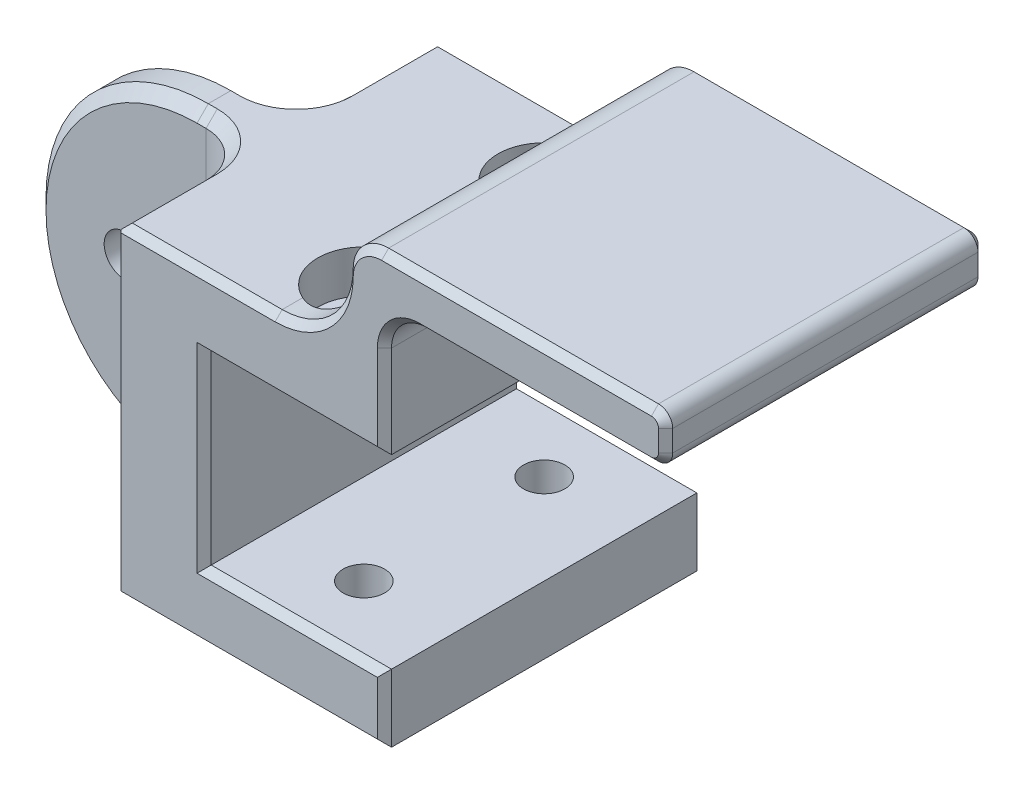
SolidWorks part; units mm, degrees
ref_plane "Front Plane" through (0, 0, 0) normal (0, 0, 1) x (1, 0, 0)
ref_plane "Top Plane" through (0, 0, 0) normal (0, 1, 0) x (1, 0, 0)
ref_plane "Right Plane" through (0, 0, 0) normal (1, 0, 0) x (0, 0, -1)
sketch "Sketch1" plane through (0, 0, 0) normal (0, 0, 1) x (1, 0, 0)
  line L0 (-22.7, -12.5) -> (2.7, -12.5)
  line L5 (2.7, -12.5) -> (2.7, 5.5)
  line L6 (2.7, 5.5) -> (42.3, 5.5)
  line L7 (42.3, 5.5) -> (42.3, 12.5)
  line L8 (42.3, 12.5) -> (-2.7, 12.5)
  line L9 (-2.7, 12.5) -> (-2.7, -2.5)
  line L10 (-2.7, -2.5) -> (-22.7, -2.5)
  line L12 (0, 12.5) -> (0, -12.5) construction
  line L13 (-2.7, 0) -> (2.7, 0) construction
  line L14 (-22.7, -12.5) -> (-22.7, -38.662)
  line L15 (-22.7, -38.662) -> (2.7, -38.662)
  line L16 (2.7, -38.662) -> (2.7, -48.187)
  line L17 (2.7, -48.187) -> (-22.7, -48.187)
  line L18 (-22.7, -48.187) -> (-35.4, -48.187)
  line L19 (-35.4, -48.187) -> (-35.4, -2.5)
  line L20 (-35.4, -2.5) -> (-22.7, -2.5)
  point P13 (0, 0)
  point P22 (0, 0)
  dimension "D1" = 18
  dimension "D2" = 45
  dimension "D3" = 25.4
  dimension "D4" = 20
  dimension "D5" = 10
  dimension "D6" = 7
  dimension "D7" = 26.162
  dimension "D8" = 9.525
  dimension "D9" = 12.7
extrude "Boss-Extrude1" add sketch "Sketch1" along normal mid plane 45
sketch "Sketch3" plane through (0, -2.5, 0) normal (0, 1, 0) x (1, 0, 0)
  line L2 (-22.7, -22.5) -> (2.7, -22.5) construction
  line L3 (-22.7, -22.5) -> (2.7, -22.5) construction
  circle A0 centre (-10, -12.7) radius 6.5
  circle A1 centre (-10, -12.7) radius 2.921
  point P3 (-10, -22.5)
  dimension "D1" = 13
  dimension "D2" = 5.842
  dimension "D3" = 12.7
extrude "Cut-Extrude1" cut sketch "Sketch3" against normal through all contours A1
extrude "Cut-Extrude2" cut sketch "Sketch3<4>" against normal blind 6
sketch "Sketch3<4>" plane through (0, -2.5, 0) normal (0, 1, 0) x (1, 0, 0) same geometry as "Sketch3"
mirror "Mirror1" about plane through (0, 0, 0) normal (0, 0, 1) of "Cut-Extrude2", "Cut-Extrude1"
sketch "Sketch9" plane through (0, 12.5, 0) normal (0, 1, 0) x (1, 0, 0)
  line L0 (25.9078, 11.1) -> (36.2078, -11.1) construction
  line L1 (42.3, -22.5) -> (42.3, 22.5) construction
  circle A0 centre (25.9078, 11.1) radius 1.0922
  circle A1 centre (36.2078, -11.1) radius 1.0922
  point P4 (31.0578, 0)
  dimension "D3" = 2.1844
  dimension "D1" = 22.2
  dimension "D2" = 10.3
  dimension "D4" = 5
extrude "Cut-Extrude3" [suppressed] cut sketch "Sketch9" against normal through all
fillet "Fillet1" radius 10 1 edges at (-2.7, -2.5, 0)
fillet "Fillet2" radius 5 2 edges at (2.7, 5.5, 0) (-2.7, 12.5, 0)
fillet "Fillet4" radius 2 2 edges at (42.3, 12.5, 0) (42.3, 5.5, 0)
chamfer "Chamfer1" distance 1 angle 45 32 edges at (42.3, 9, 22.5) (24, 5.5, 22.5) (4.1645, 4.0355, 22.5) (2.7, -6, 22.5) (-10, -12.5, 22.5) (-24.05, -2.5, 22.5) (-5.6289, 0.4289, 22.5) (21.3, 12.5, 22.5) (-24.05, -2.5, -22.5) (-10, -12.5, -22.5) (2.7, -6, -22.5) (4.1645, 4.0355, -22.5) (24, 5.5, -22.5) (42.3, 9, -22.5) (21.3, 12.5, -22.5) (-5.6289, 0.4289, -22.5) (41.7142, 6.0858, 22.5) (41.7142, 11.9142, 22.5) (41.7142, 6.0858, -22.5) (41.7142, 11.9142, -22.5) (-1.2355, 11.0355, 22.5) (-1.2355, 11.0355, -22.5) (-22.7, -25.581, 22.5) (-10, -38.662, 22.5) (2.7, -43.4245, 22.5) (-16.35, -48.187, 22.5) (-16.35, -48.187, -22.5) (2.7, -43.4245, -22.5) (-10, -38.662, -22.5) (-22.7, -25.581, -22.5) (-35.4, -25.3435, 22.5) (-35.4, -25.3435, -22.5)
sketch "Sketch11" plane through (-35.4, 0, 0) normal (-1, 0, 0) x (0, 0, 1)
  line L0 (0, -48.187) -> (0, -2.5) construction
  line L1 (21.5, -48.187) -> (-21.5, -48.187) construction
  line L2 (21.5, -2.5) -> (-21.5, -2.5) construction
  line L4 (3.175, -48.187) -> (-3.175, -48.187)
  line L5 (3.175, -48.187) -> (3.175, -2.5)
  line L6 (3.175, -2.5) -> (-3.175, -2.5)
  line L7 (-3.175, -48.187) -> (-3.175, -2.5)
  point P10 (0, -48.187)
  dimension "D1" = 6.35
  dimension "D2" = 45.687
extrude "Boss-Extrude2" add sketch "Sketch11" along normal blind 30.48
fillet "Fillet5" radius 6.35 2 edges at (-35.4, -25.3435, -3.175) (-35.4, -25.3435, 3.175)
fillet "Fillet6" radius 22.86 2 edges at (-65.88, -2.5, 0) (-65.88, -48.187, 0)
sketch "Sketch12" plane through (0, 0, 3.175) normal (0, 0, 1) x (1, 0, 0)
  line L0 (-41.75, -25.3435) -> (-65.88, -25.3435) construction
  line L1 (-41.75, -48.187) -> (-41.75, -2.5) construction
  circle A0 centre (-53.18, -25.3435) radius 2.921
  dimension "D1" = 5.842
  dimension "D2" = 11.43
extrude "Cut-Extrude4" cut sketch "Sketch12" against normal through all
chamfer "Chamfer2" distance 1.5875 angle 45 16 edges at (-35.4, -48.187, -15.5125) (-37.2599, -48.187, -5.0349) (-42.385, -48.187, -3.175) (-35.4, -2.5, -15.5125) (-59.1786, -41.4973, -3.175) (-59.1786, -9.1897, -3.175) (-42.385, -2.5, -3.175) (-37.2599, -2.5, -5.0349) (-35.4, -48.187, 15.5125) (-37.2599, -48.187, 5.0349) (-42.385, -48.187, 3.175) (-59.1786, -41.4973, 3.175) (-59.1786, -9.1897, 3.175) (-42.385, -2.5, 3.175) (-37.2599, -2.5, 5.0349) (-35.4, -2.5, 15.5125)
